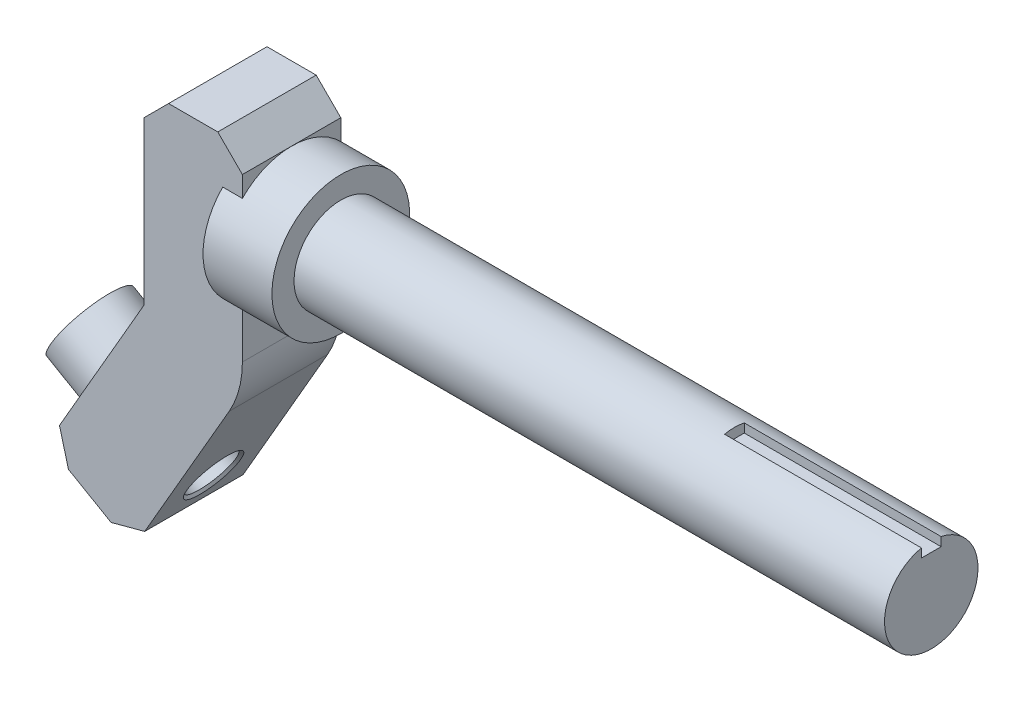
SolidWorks part; units mm, degrees
ref_plane "Piano frontale" through (0, 0, 0) normal (0, 0, 1) x (1, 0, 0)
ref_plane "Piano superiore" through (0, 0, 0) normal (0, 1, 0) x (1, 0, 0)
ref_plane "Piano destro" through (0, 0, 0) normal (1, 0, 0) x (0, 0, -1)
sketch "Schizzo1" plane through (0, 0, 0) normal (1, 0, 0) x (0, 0, -1)
  circle A0 centre (0, 0) radius 9.5
  dimension "D1" = 19
extrude "Estrusione-Estrusione1" add sketch "Schizzo1" along normal blind 120
sketch "Schizzo2" plane through (120, 0, 0) normal (1, 0, 0) x (0, 0, -1)
  line L0 (-2, 9.2871) -> (-2, 7.5)
  line L1 (-2, 7.5) -> (2, 7.5)
  line L2 (2, 7.5) -> (2, 9.2871)
  circle A1 centre (0, 0) radius 9.5
  arc A2 (2, 9.2871) -> (-2, 9.2871) centre (0, 0) ccw
  point P6 (0, 7.5)
  dimension "D2" = 4
  dimension "D3" = 7.5
  dimension "D1" = 0
extrude "Taglio-Estrusione1" cut sketch "Schizzo2" against normal blind 40
sketch "Schizzo3" plane through (0, 0, 0) normal (-1, 0, 0) x (0, 0, 1)
  circle A0 centre (0, 0) radius 14
  dimension "D1" = 28
extrude "Estrusione-Estrusione2" add sketch "Schizzo3" along normal blind 14
sketch "Schizzo4" plane through (0, 0, 0) normal (0, 0, 1) x (1, 0, 0)
  line L0 (-146.192, 0) -> (146.192, 0) construction
  line L5 (-10, 19) -> (-10, 9.5)
  line L9 (-10, -9.5) -> (-10, -19)
  line L10 (120, -9.5) -> (120, 9.2871) construction
  line L11 (-10, 19) -> (-30, 19)
  line L12 (-12.6795, -29) -> (-32.3523, -63.0742)
  line L13 (-30, 19) -> (-30, -19)
  line L14 (-115.6, 0) -> (-25.8523, -51.8159) construction
  line L15 (0, 14) -> (-14, 14) construction
  line L16 (-32.3523, -63.0742) -> (-49.6728, -53.0742)
  line L17 (0, 9.5) -> (-30, 9.5) construction
  line L18 (-30, -19) -> (-49.6728, -53.0742)
  line L25 (-10, 9.5) -> (-15, 9.5)
  line L26 (-15, 9.5) -> (-15, -9.5)
  line L27 (-15, -9.5) -> (-10, -9.5)
  line L28 (0, -9.5) -> (-30, -9.5) construction
  arc A1 (-10, -19) -> (-12.6795, -29) centre (-30, -19) cw
  point P2 (-115.6, 0)
  point P19 (0, 0)
  dimension "D7" = 20
  dimension "D8" = 20
  dimension "D1" = 20
  dimension "D2" = 150
  dimension "D3" = 13
  dimension "D4" = 85.6
  dimension "D5" = 30
  dimension "D6" = 5
extrude "Estrusione-Estrusione3" add sketch "Schizzo4" along normal mid plane 20
chamfer "Smusso1" distance 5 angle 45 2 edges at (-30, 19, 0) (-10, 19, 0)
chamfer "Smusso2" distance 2 angle 45 2 edges at (-15, 9.5, 0) (-15, -9.5, 0)
chamfer "Smusso3" distance 5 angle 45 2 edges at (-49.6728, -53.0742, 0) (-32.3523, -63.0742, 0)
sketch "Schizzo6" plane through (0, 0, 0) normal (0, 0, 1) x (1, 0, 0)
  line L0 (-43.1728, -41.8159) -> (-25.8523, -51.8159)
  line L1 (-30, -19) -> (-49.6728, -53.0742) construction
  line L2 (-115.6, 0) -> (-25.8523, -51.8159) construction
  line L3 (-25.8523, -51.8159) -> (-23.3523, -47.4858)
  line L4 (-12.6795, -29) -> (-32.3523, -63.0742) construction
  line L5 (-23.3523, -47.4858) -> (-40.6728, -37.4858)
  line L6 (-40.6728, -37.4858) -> (-43.1728, -41.8159)
  dimension "D1" = 5
revolve "Taglia-Rivoluzione1" cut sketch "Schizzo6" angle 360 about L14
chamfer "Smusso4" distance 0.5 angle 45 1 edges at (-28.3523, -56.146, 0)
sketch "Schizzo7" plane through (-14.2728, 8.2404, 0) normal (-0.866, 0.5, 0) x (0, 0, 1)
  circle A0 centre (0, -57.8) radius 8
  circle A1 centre (0, -57.8) radius 5 construction
  circle A2 centre (0, -57.8) radius 5
  dimension "D1" = 16
extrude "Estrusione-Estrusione4" add sketch "Schizzo7" along normal blind 9
chamfer "Smusso5" distance 0.5 angle 45 1 edges at (-53.467, -41.646, 0)
